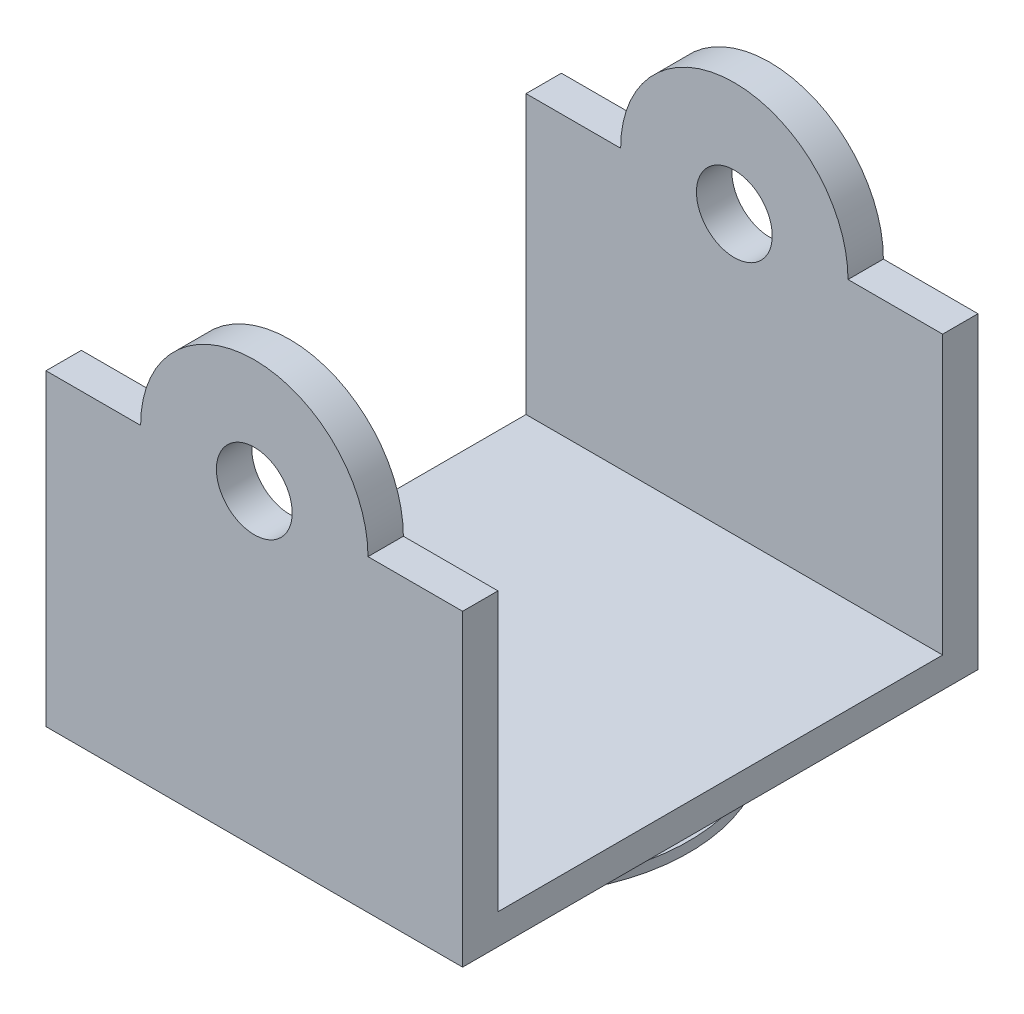
SolidWorks part; units mm, degrees
ref_plane "Front Plane" through (0, 0, 0) normal (0, 0, 1) x (1, 0, 0)
ref_plane "Top Plane" through (0, 0, 0) normal (0, 1, 0) x (1, 0, 0)
ref_plane "Right Plane" through (0, 0, 0) normal (1, 0, 0) x (0, 0, -1)
sketch "Sketch1" plane through (0, 0, 0) normal (0, 1, 0) x (1, 0, 0)
  line L1 (-41.225, 44) -> (41.225, 44)
  line L2 (-41.225, 44) -> (-41.225, -44)
  line L3 (-41.225, -44) -> (41.225, -44)
  line L4 (41.225, 44) -> (41.225, -44)
  line L5 (-41.225, 44) -> (41.225, -44) construction
  line L6 (-41.225, -44) -> (41.225, 44) construction
  point P0 (0, 0)
  dimension "D1" = 88
  dimension "D2" = 82.45
extrude "Boss-Extrude1" add sketch "Sketch1" against normal blind 6 contours L4 L3 L2 L1
sketch "Sketch2" plane through (0, 0, 0) normal (0, 1, 0) x (1, 0, 0)
  line L0 (-41.225, 44) -> (-41.225, 51)
  line L1 (-41.225, 51) -> (41.225, 51)
  line L2 (41.225, 51) -> (41.225, 44)
  line L3 (41.225, 44) -> (-41.225, 44)
  line L4 (-41.225, -44) -> (-41.225, -51)
  line L5 (-41.225, -51) -> (41.225, -51)
  line L6 (41.225, -51) -> (41.225, -44)
  line L7 (41.225, -44) -> (-41.225, -44)
  dimension "D1" = 7
  dimension "D2" = 7
  dimension "D3" = 7
extrude "Boss-Extrude2" add sketch "Sketch2" along normal blind 55 separate body
extrude "Boss-Extrude3" add sketch "Sketch2<2>" against normal blind 6 contours L3 L0 L1 L2
sketch "Sketch2<2>" plane through (0, 0, 0) normal (0, 1, 0) x (1, 0, 0) same geometry as "Sketch2"
extrude "Boss-Extrude4" add sketch "Sketch2<3>" against normal blind 6 contours L5 L6 L7 L4
sketch "Sketch2<3>" plane through (0, 0, 0) normal (0, 1, 0) x (1, 0, 0) same geometry as "Sketch2"
sketch "Sketch4" plane through (0, 0, -44) normal (0, 0, 1) x (1, 0, 0)
  line L2 (-41.225, 55) -> (41.225, 55) construction
  line L3 (22.5, 55) -> (-22.5, 55)
  arc A1 (22.5, 55) -> (-22.5, 55) centre (0, 55) ccw
  dimension "D1" = 45
extrude "Boss-Extrude5" add sketch "Sketch4" against normal blind 7
sketch "Sketch5" plane through (0, 0, 44) normal (0, 0, -1) x (-1, 0, 0)
  line L2 (-41.225, 55) -> (41.225, 55) construction
  line L3 (22.5, 55) -> (-22.5, 55)
  arc A1 (22.5, 55) -> (-22.5, 55) centre (0, 55) ccw
  dimension "D1" = 45
extrude "Boss-Extrude7" add sketch "Sketch5" against normal blind 7
sketch "Sketch8" plane through (0, -6, 0) normal (0, -1, 0) x (1, 0, 0)
  line L0 (41.225, 0) -> (-41.225, 0)
  line L1 (41.225, 51) -> (41.225, -51) construction
  line L2 (-41.225, -51) -> (-41.225, 51) construction
  circle A0 centre (0, 0) radius 32.5
  dimension "D1" = 65
extrude "Boss-Extrude8" add sketch "Sketch8" along normal blind 7 contours A0
sketch "Sketch9" plane through (0, -13, 0) normal (0, -1, 0) x (1, 0, 0)
  circle A0 centre (0, 0) radius 35
  dimension "D1" = 70
extrude "Boss-Extrude9" add sketch "Sketch9" along normal blind 2
sketch "Sketch10" plane through (0, 0, -44) normal (0, 0, 1) x (1, 0, 0)
  circle A0 centre (0, 55) radius 7.5
  dimension "D1" = 15
extrude "Cut-Extrude3" cut sketch "Sketch10" against normal up to surface (7 mm away) contours A0 up to face at (0, 38.4167, -51)
sketch "Sketch11" plane through (0, 0, 44) normal (0, 0, -1) x (-1, 0, 0)
  circle A0 centre (0, 55) radius 7.5
  dimension "D1" = 15
extrude "Cut-Extrude4" cut sketch "Sketch11" against normal up to surface (7 mm away) up to face at (0, 38.4167, 51)
